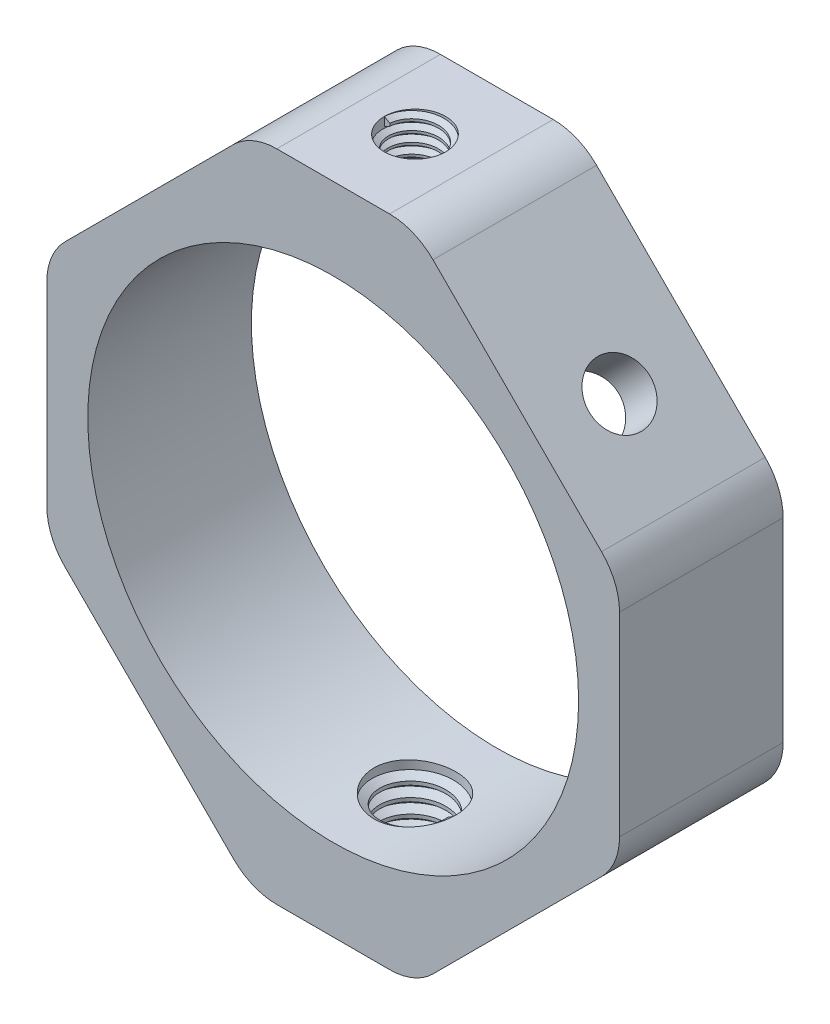
SolidWorks part; units mm, degrees
ref_plane "Front Plane" through (0, 0, 0) normal (0, 0, 1) x (1, 0, 0)
ref_plane "Top Plane" through (0, 0, 0) normal (0, 1, 0) x (1, 0, 0)
ref_plane "Right Plane" through (0, 0, 0) normal (1, 0, 0) x (0, 0, -1)
sketch "Sketch1" plane through (0, 0, 0) normal (0, 0, 1) x (1, 0, 0)
  line L0 (-4, 16) -> (4, 16)
  line L1 (4, 16) -> (14, 6)
  line L2 (14, 6) -> (14, -6)
  line L3 (14, -6) -> (4, -16)
  line L4 (4, -16) -> (-4, -16)
  line L5 (-4, -16) -> (-14, -6)
  line L6 (-14, -6) -> (-14, 6)
  line L7 (-14, 6) -> (-4, 16)
  circle A0 centre (0, 0) radius 12
  point P10 (14, 0)
  point P12 (-14, 0)
  point P13 (0, 0)
  point P14 (0, 16)
  point P15 (0, -16)
  point P16 (-5.491, -12.9962)
  dimension "D1" = 12
  dimension "D3" = 24
  dimension "D2" = 12
  dimension "D4" = 14
  dimension "D5" = 14
  dimension "D6" = 16
  dimension "D7" = 16
  dimension "D8" = 45
extrude "Boss-Extrude1" add sketch "Sketch1" along normal blind 8
sketch "Sketch2" plane through (0, 16, 0) normal (0, 1, 0) x (1, 0, 0)
  circle A0 centre (0, -4) radius 1.5
  dimension "D1" = 3
extrude "Cut-Extrude1" cut sketch "Sketch2" against normal blind 8
ref_plane "Plane1" through (0, 0, 4) normal (0, 0, 1) x (1, 0, 0)
sketch "Sketch3" plane through (0, 0, 4) normal (0, 0, 1) x (1, 0, 0)
  line L0 (0, 9.7282) -> (0, 0) construction
  line L1 (0, 0) -> (13.8923, 13.8923) construction
  line L2 (10, 10) -> (11.0607, 8.9393)
  line L3 (14, 6) -> (4, 16) construction
  line L4 (11.0607, 8.9393) -> (9.0254, 6.904)
  line L5 (9.0254, 6.904) -> (7.9647, 7.9647)
  line L6 (7.9647, 7.9647) -> (10, 10)
  dimension "D1" = 45
  dimension "D2" = 1.5
revolve "Cut-Revolve1" cut sketch "Sketch3" angle 360 about L6
sketch "Sketch4" plane through (0, -16, 0) normal (0, -1, 0) x (-1, 0, 0)
  circle A0 centre (0, -4) radius 2
  dimension "D1" = 4
extrude "Cut-Extrude2" cut sketch "Sketch4" against normal blind 8
thread "Thread1" pitch 0.5 method extrude profile "Thread Profile1" start angle 0, offset 0, length 3.5, pitch 0.5, diameter 3
ref_plane "Plane2" through (-1.5, 16, 4) normal (0, 0, 1) x (-1, 0, 0)
sketch "Thread Profile1" plane through (-1.5, 16, 4) normal (0, 0, 1) x (-1, 0, 0)
  line L0 (0, 0) -> (0, 0.5) construction
  line L11 (0, 0) -> (0, 0.4375)
  line L12 (0, 0.4375) -> (-0.2706, 0.2812)
  line L13 (-0.2706, 0.2812) -> (-0.2706, 0.1562)
  line L15 (-0.2706, 0.1562) -> (0, 0)
  line L17 (-0.2706, 0.2187) -> (0, 0.2187) construction
  point P2 (0, 0)
  dimension "Pitch" = 0.5
  dimension "Profile_Angle" = 60
  dimension "Profile_Land" = 0.125
  dimension "Profile_Height" = 0.2706
thread "Thread2" pitch 0.7 method extrude profile "Thread Profile2" start angle 0, offset 0, length 3.5, pitch 0.7, diameter 4
ref_plane "Plane3" through (2, -16, 4) normal (0, 0, 1) x (1, 0, 0)
sketch "Thread Profile2" plane through (2, -16, 4) normal (0, 0, 1) x (1, 0, 0)
  line L0 (0, 0) -> (0, 0.7) construction
  line L11 (0, 0) -> (0, 0.6125)
  line L12 (0, 0.6125) -> (-0.3789, 0.3937)
  line L13 (-0.3789, 0.3937) -> (-0.3789, 0.2187)
  line L15 (-0.3789, 0.2187) -> (0, 0)
  line L17 (-0.3789, 0.3062) -> (0, 0.3062) construction
  point P2 (0, 0)
  dimension "Pitch" = 0.7
  dimension "Profile_Angle" = 60
  dimension "Profile_Land" = 0.175
  dimension "Profile_Height" = 0.3789
fillet "Fillet1" radius 3 8 edges at (-14, 6, 4) (-14, -6, 4) (-4, -16, 4) (4, -16, 4) (14, -6, 4) (14, 6, 4) (4, 16, 4) (-4, 16, 4)
